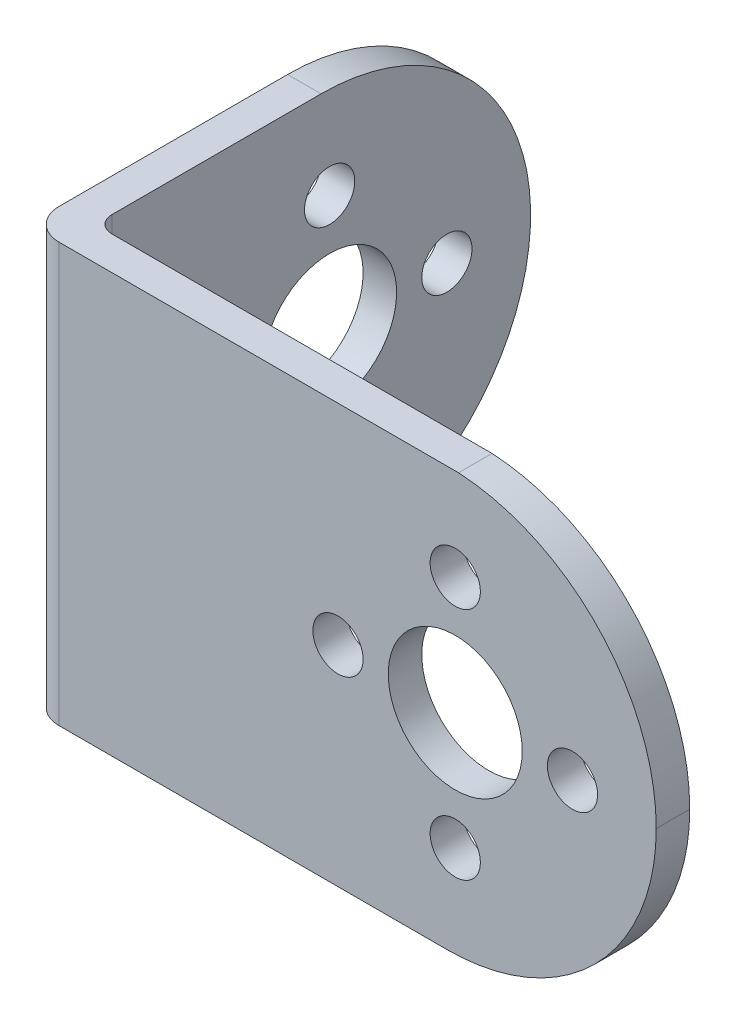
SolidWorks part; units mm, degrees
ref_plane "Alzado" through (0, 0, 0) normal (0, 0, 1) x (1, 0, 0)
ref_plane "Planta" through (0, 0, 0) normal (0, 1, 0) x (1, 0, 0)
ref_plane "Vista lateral" through (0, 0, 0) normal (1, 0, 0) x (0, 0, -1)
sketch "Croquis1" plane through (0, 0, 0) normal (0, 1, 0) x (1, 0, 0)
  line L0 (0, 1.84) -> (0, 28)
  line L1 (0, 28) -> (2, 28)
  line L2 (2, 28) -> (2, 3)
  line L3 (3, 2) -> (37.5, 2)
  line L4 (37.5, 2) -> (37.5, 0)
  line L5 (37.5, 0) -> (1.84, 0)
  arc A0 (0, 1.84) -> (1.84, 0) centre (1.84, 1.84) ccw
  arc A1 (2, 3) -> (3, 2) centre (3, 3) ccw
  point P9 (0, 0)
  dimension "D5" = 1.84
  dimension "D6" = 1
  dimension "D1" = 2
  dimension "D2" = 2
  dimension "D3" = 28
  dimension "D4" = 37.5
extrude "Saliente-Extruir1" add sketch "Croquis1" along normal blind 25
sketch "Croquis2" plane through (0, 0, 0) normal (-1, 0, 0) x (0, 0, 1)
  line L0 (-28, 25) -> (-28, 0) construction
  line L1 (-28, 25) -> (-1.84, 25) construction
  line L2 (-28, 12.49) -> (-16, 12.49) construction
  line L3 (-15.49, 25) -> (-28, 25)
  line L4 (-28, 25) -> (-28, 0)
  line L5 (-28, 0) -> (-15.49, -0.02)
  circle A0 centre (-15.49, 12.49) radius 12.51
  circle A1 centre (-16, 12.49) radius 4
  circle A2 centre (-23, 12.49) radius 1.5
  circle A3 centre (-9, 12.49) radius 1.5
  circle A4 centre (-16, 19.49) radius 1.5
  circle A5 centre (-16, 5.49) radius 1.5
  dimension "D1" = 12
  dimension "D2" = 7
  dimension "D3" = 14
  dimension "D4" = 7
  dimension "D5" = 14
extrude "Cortar-Extruir1" cut sketch "Croquis2" against normal blind 25
sketch "Croquis3" plane through (0, 0, 0) normal (0, 0, 1) x (1, 0, 0)
  line L0 (37.5, 12.5) -> (25.5, 12.5) construction
  line L1 (37.5, 25) -> (37.5, 0) construction
  line L2 (1.84, 0) -> (37.5, 0) construction
  line L3 (24.99, 25.02) -> (37.5, 25)
  line L4 (37.5, 25) -> (37.5, 0)
  line L5 (37.5, 0) -> (24.99, 0)
  circle A0 centre (25.5, 12.5) radius 4
  circle A1 centre (25.5, 19.5) radius 1.5
  circle A2 centre (32.5, 12.5) radius 1.5
  circle A3 centre (18.5, 12.5) radius 1.5
  circle A4 centre (25.5, 5.5) radius 1.5
  circle A5 centre (24.99, 12.51) radius 12.51
  dimension "D2" = 14
  dimension "D1" = 12
  dimension "D3" = 7
  dimension "D4" = 14
  dimension "D5" = 7
extrude "Cortar-Extruir2" cut sketch "Croquis3" against normal blind 25
